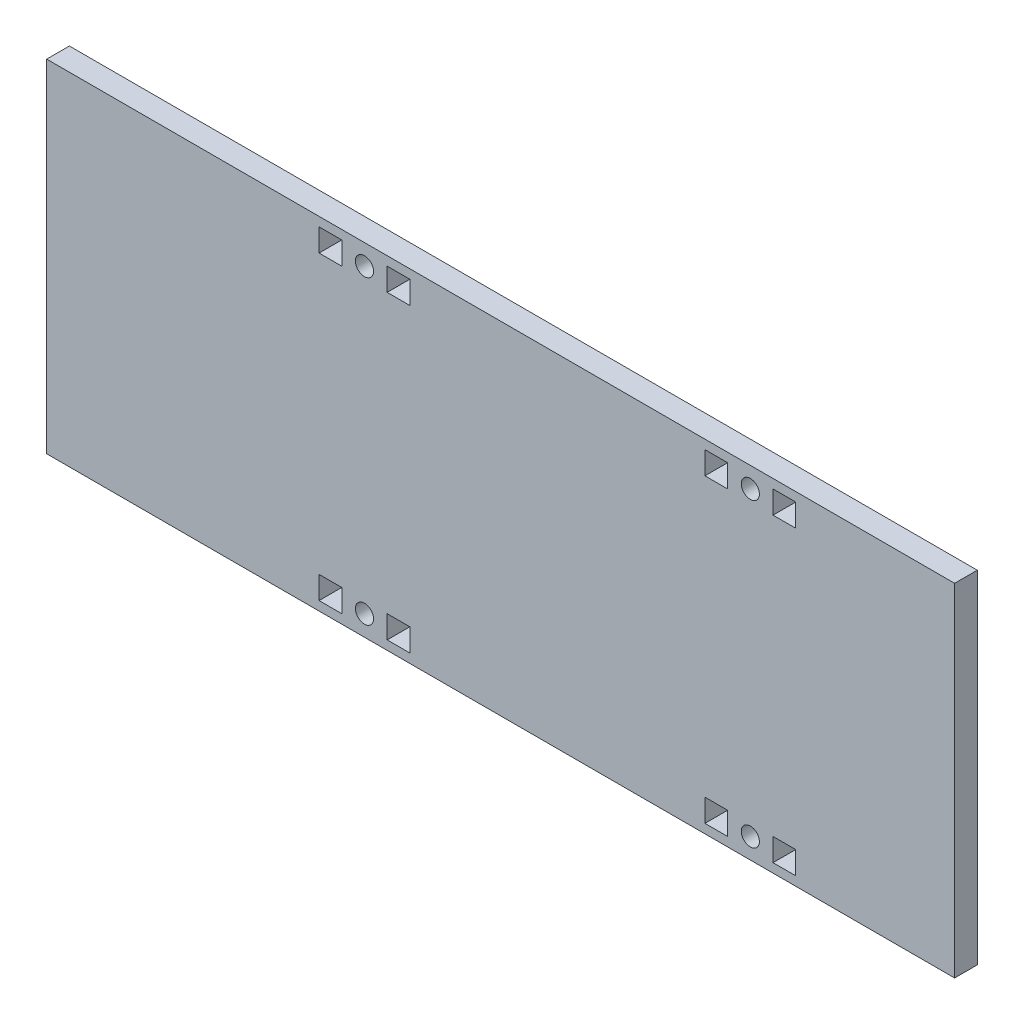
SolidWorks part; units mm, degrees
ref_plane "Plan de face" through (0, 0, 0) normal (0, 0, 1) x (1, 0, 0)
ref_plane "Plan de dessus" through (0, 0, 0) normal (0, 1, 0) x (1, 0, 0)
ref_plane "Plan de droite" through (0, 0, 0) normal (1, 0, 0) x (0, 0, -1)
sketch "Esquisse1" plane through (0, 0, 0) normal (0, 0, 1) x (1, 0, 0)
  line L0 (0, 0) -> (200, 0) construction
  line L1 (0, 37.65) -> (200, 37.65)
  line L2 (200, 37.65) -> (200, -37.65)
  line L3 (0, 37.65) -> (0, -37.65)
  line L4 (0, -37.65) -> (200, -37.65)
  point P3 (0, 0)
  point P7 (0, 0)
  line B0 (65, 33.15) -> (75, 33.15) construction
  line B1 (65, 35.65) -> (60, 35.65)
  line B2 (65, 35.65) -> (65, 30.65)
  line B3 (65, 30.65) -> (60, 30.65)
  line B4 (60, 35.65) -> (60, 30.65)
  line B5 (75, 35.65) -> (80, 35.65)
  line B6 (75, 35.65) -> (75, 30.65)
  line B7 (75, 30.65) -> (80, 30.65)
  line B8 (80, 35.65) -> (80, 30.65)
  line B9 (70, 33.15) -> (70, 40.1224) construction
  circle B10 centre (70, 33.15) radius 2
  line B11 (150, 33.15) -> (160, 33.15) construction
  line B12 (150, 35.65) -> (145, 35.65)
  line B13 (150, 35.65) -> (150, 30.65)
  line B14 (150, 30.65) -> (145, 30.65)
  line B15 (145, 35.65) -> (145, 30.65)
  line B16 (160, 35.65) -> (165, 35.65)
  line B17 (160, 35.65) -> (160, 30.65)
  line B18 (160, 30.65) -> (165, 30.65)
  line B19 (165, 35.65) -> (165, 30.65)
  line B20 (155, 33.15) -> (155, 40.1224) construction
  circle B21 centre (155, 33.15) radius 2
  line B22 (150, -35.65) -> (145, -35.65)
  line B23 (150, -35.65) -> (150, -30.65)
  line B24 (150, -30.65) -> (145, -30.65)
  line B25 (145, -35.65) -> (145, -30.65)
  line B26 (160, -35.65) -> (165, -35.65)
  line B27 (160, -35.65) -> (160, -30.65)
  line B28 (160, -30.65) -> (165, -30.65)
  line B29 (165, -35.65) -> (165, -30.65)
  circle B30 centre (155, -33.15) radius 2
  line B31 (65, -35.65) -> (60, -35.65)
  line B32 (65, -35.65) -> (65, -30.65)
  line B33 (65, -30.65) -> (60, -30.65)
  line B34 (60, -35.65) -> (60, -30.65)
  line B35 (75, -35.65) -> (80, -35.65)
  line B36 (75, -35.65) -> (75, -30.65)
  line B37 (75, -30.65) -> (80, -30.65)
  line B38 (80, -35.65) -> (80, -30.65)
  circle B39 centre (70, -33.15) radius 2
  dimension "D1" = 85
  dimension "D2" = 45
  dimension "D3" = 2
  dimension "D4" = 200
  dimension "D5" = 33.15
sketch_block_instance "Trou M4 plots 5mm-1"
sketch_block "Trou M4 plots 5mm" parameters "D2"=4, "D1"=5, "D3"=5, "D4"=10
sketch_block_instance "Trou M4 plots 5mm-2"
sketch_block_instance "Trou M4 plots 5mm-4"
sketch_block_instance "Trou M4 plots 5mm-5"
extrude "Boss.-Extru.1" add sketch "Esquisse1" along normal blind 5
